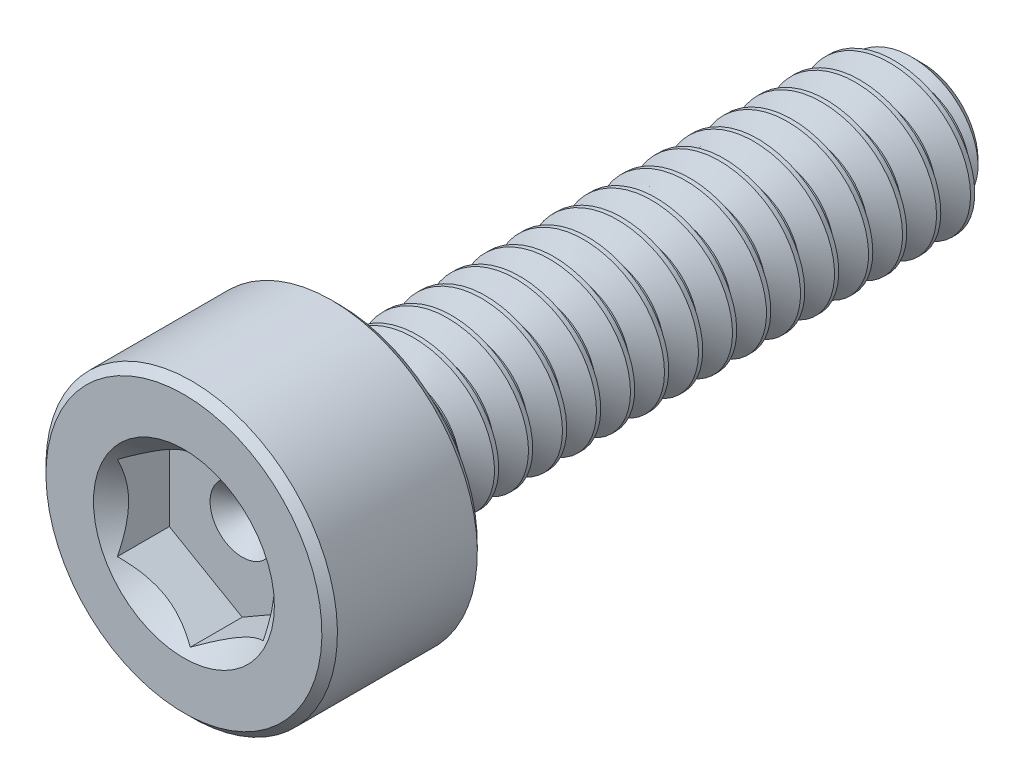
SolidWorks part; units mm, degrees
ref_plane "Front Plane" through (0, 0, 0) normal (0, 0, 1) x (1, 0, 0)
ref_plane "Top Plane" through (0, 0, 0) normal (0, 1, 0) x (1, 0, 0)
ref_plane "Right Plane" through (0, 0, 0) normal (1, 0, 0) x (0, 0, -1)
sketch "Sketch1" plane through (0, 0, 0) normal (1, 0, 0) x (0, 0, -1)
  line L0 (-3.8, 0) -> (3.8, 0) construction
  line L1 (3.8, 0) -> (3.8, 0.5727) construction
  line L2 (3.8, 0.5727) -> (3.5727, 0.8) construction
  line L3 (3.5727, 0.8) -> (3.5375, 0.8) construction
  line L4 (3.5375, 0.8) -> (-2.2, 0.8) construction
  line L5 (-2.2, 0.8) -> (-2.2, 1.5) construction
  line L6 (-2.2, 1.5) -> (-3.8, 1.5) construction
  line L7 (-3.8, 1.5) -> (-3.8, 0) construction
  line L8 (3.8, 0.5727) -> (3.8, 0.8) construction
  line L9 (3.7781, 0.8379) -> (3.9531, 0.5348) construction
  line L10 (3.9531, 0.5348) -> (4.1281, 0.8379) construction
  line L11 (4.1281, 0.8379) -> (3.7781, 0.8379) construction
  line L12 (3.9531, 0.8379) -> (3.9531, 0.8) construction
  line L13 (3.9531, 0.5348) -> (3.9531, 0.5727) construction
  line L14 (3.9312, 0.5727) -> (3.975, 0.5727) construction
  line L15 (3.8, 0.8) -> (4.1063, 0.8) construction
  line L16 (3.7891, 0.8189) -> (4.1172, 0.8189) construction
  line L17 (3.8, 0) -> (3.8, -0.8) construction
  line L18 (-2.28, 1.5) -> (-2.2, 1.42) construction
  line L19 (-3.72, 1.5) -> (-3.8, 1.42) construction
  line L20 (-2.2, 0.8) -> (-2.2, 0) construction
  line L21 (-2.2, 0.4) -> (-0.2, 0.4) construction
  line L22 (-0.2, 0.4) -> (1.8, 0.4) construction
  line L23 (1.8, 0.4) -> (3.8, 0.4) construction
  line L24 (-0.2, 0.4) -> (-0.2, 0.8) construction
  line L25 (-0.2, 0.8) -> (-0.2, 1.5) construction
  line L26 (1.8, 0.4) -> (1.8, 1.5) construction
  point P0 (-3.8, 0.75)
  point P3 (2.925, 0.8)
  point P4 (0, 0)
  point P18 (1.8, 0.8)
  point P22 (3.9531, 0.5727)
  point P24 (3.5375, 0.8)
  point P25 (3.9531, 0.8)
  point P28 (3.9531, 0.8189)
  point P29 (2.925, -0.8)
  point P30 (-0.2, 0.8)
  point P31 (-3, 1.5)
  point P37 (-2.48, 1.5)
  point P38 (-3.68, 1.5)
  point P45 (-0.2, 0.4)
  point P46 (1.8, 0.4)
  dimension "D2" = 0.0437
  dimension "D7" = 0.08
  dimension "D8" = 0.08
  dimension "D9" = 0.08
  dimension "D10" = 0.04
  dimension "D11" = 0.2
  dimension "Drive Size" = 1.5
  dimension "Head Diameter" = 3
  dimension "Head Height" = 1.6
  dimension "Thread Pitch" = 0.35
  dimension "Thread Dia" = 1.6
  dimension "Length" = 6
  dimension "D12" = 0.2625
  dimension "D4" = 0.875
  dimension "D3" = 45
sketch "Sketch2" plane through (0, 0, 0) normal (1, 0, 0) x (0, 0, -1)
  line L0 (-3.8, 0) -> (-3.8, 1.42)
  line L1 (-3.72, 1.5) -> (-2.28, 1.5)
  line L2 (-2.2, 1.42) -> (-2.2, 0.88)
  line L4 (3.5727, 0.8) -> (3.8, 0.5727)
  line L5 (3.8, 0.5727) -> (3.8, 0)
  line L6 (-2.2, 1.5) -> (-3.8, 1.5) construction
  line L7 (3.8, 0) -> (-3.8, 0)
  line L8 (-3.72, 1.5) -> (-3.8, 1.42) construction
  line L10 (-3.72, 1.5) -> (-3.8, 1.42)
  line L14 (-2.28, 1.5) -> (-2.2, 1.42) construction
  line L16 (-2.28, 1.5) -> (-2.2, 1.42)
  line L17 (-2.2, 0.8) -> (-2.2, 1.5) construction
  line L19 (-2.12, 0.8) -> (3.5727, 0.8)
  line L20 (3.5375, 0.8) -> (-2.2, 0.8) construction
  arc A1 (-2.2, 0.88) -> (-2.12, 0.8) centre (-2.12, 0.88) ccw
  dimension "D3" = 0.08
revolve "Revolve1" add sketch "Sketch2" angle 360 about L7
sketch "Sketch3" plane through (0, 0, 3.8) normal (0, 0, 1) x (1, 0, 0)
  line L1 (0.75, -0.433) -> (0.75, 0.433)
  line L2 (0.75, 0.433) -> (0, 0.866)
  line L3 (0, 0.866) -> (-0.75, 0.433)
  line L4 (-0.75, 0.433) -> (-0.75, -0.433)
  line L5 (-0.75, -0.433) -> (0, -0.866)
  line L6 (0, -0.866) -> (0.75, -0.433)
  circle A0 centre (0, 0) radius 0.75 construction
  circle A1 centre (0, 0) radius 1.5 construction
  circle A2 centre (0, 0) radius 1.5 construction
  circle A3 centre (0, 0) radius 0.866 construction
  point P13 (0, 0)
  dimension "D1" = 1.7321
extrude "Cut-Extrude1" cut sketch "Sketch3" against normal offset from surface (0.6 mm away) 1 up to face at (0, 1.42, 2.2)
sketch "Sketch4" plane through (0, 0, 3.8) normal (0, 0, 1) x (1, 0, 0)
  circle A0 centre (0, 0) radius 0.931
  dimension "D1" = 1.862
extrude "Cut-Extrude2" cut sketch "Sketch4" against normal up to vertex (0.8 mm away) draft 45 up to point (0, 1.5, 3)
sketch "Sketch11" plane through (0, 0, 0) normal (1, 0, 0) x (0, 0, -1)
  line L0 (-3.8, 0) -> (3.8, 0) construction
  line L1 (-3.8, 0) -> (3.8, 0) construction
  line L2 (-1.075, 0) -> (-1.075, 0.8) construction
  line L3 (3.5375, 0.8) -> (-2.2, 0.8) construction
  line L4 (2.675, 0) -> (2.675, 0.8) construction
  line L6 (3.8, 0.5727) -> (3.8, 0.8) construction
  point P2 (-1.075, 0)
  point P3 (2.675, 0)
  dimension "D1" = 1.125
  dimension "D2" = 1.125
sketch "Sketch6" plane through (0, 0, -3.8) normal (0, 0, -1) x (-1, 0, 0)
  circle A0 centre (0, 0) radius 0.8
curve "Helix/Spiral1" pitch 0.35 height 6.35 turns 18.1429
sketch "Sketch10" plane through (0, 0, 0) normal (1, 0, 0) x (0, 0, -1)
  line L0 (-2.12, -1.5) -> (-2.12, 1.5)
  line L5 (-3.8, 0) -> (3.8, 0) construction
  line L6 (-2.12, 0.8) -> (-2.12, -0.8) construction
  point P3 (-2.12, 0)
split "Split1" trim tools "Sketch10" bodies to split 106 resulting bodies 114 115
sketch "Sketch7" plane through (0, 0, 0) normal (1, 0, 0) x (0, 0, -1)
  line L0 (3.7891, 0.8189) -> (4.1172, 0.8189)
  line L1 (4.1172, 0.8189) -> (3.975, 0.5727)
  line L2 (3.975, 0.5727) -> (3.9312, 0.5727)
  line L3 (3.9312, 0.5727) -> (3.7891, 0.8189)
sweep "Cut-Sweep1" cut profiles "Sketch7" path "Helix/Spiral1" align with end faces yes
sketch "Sketch8" plane through (0, 0, 0) normal (1, 0, 0) x (0, 0, -1)
  line L0 (-2.2, 0) -> (-2.2, 0.8)
  line L1 (-2.12, -0.8) -> (-2.12, 0.8) construction
  line L2 (-2.2, 0.8) -> (-2.12, 0.8)
  line L4 (-2.12, 0.8) -> (-1.6581, 0)
  line L5 (-1.6581, 0) -> (-2.2, 0)
  line L6 (3.5375, 0.8) -> (-2.2, 0.8) construction
  line L7 (-3.8, 0) -> (3.8, 0) construction
  dimension "D1" = 60
revolve "Revolve2" add sketch "Sketch8" angle 360 about L5
equation "\"D2@Sketch1\" = \"Thread Pitch@Sketch1\" / 8"
equation "\"D4@Helix/Spiral1\" = \"Thread Pitch@Sketch1\""
equation "\"D7@Sketch1\" = \"Head Height@Sketch1\" * .05"
equation "\"D8@Sketch1\"=\"D7@Sketch1\""
equation "\"D9@Sketch1\"=\"D7@Sketch1\""
equation "\"D10@Sketch1\"=\"D7@Sketch1\"/2"
equation "\"D11@Sketch1\"=\"D10@Sketch1\"*5"
equation "\"D4@Sketch1\"=\"Thread Pitch@Sketch1\"*2.5"
equation "\"D12@Sketch1\"=\"Thread Pitch@Sketch1\"*.75"
equation "\"D3@Helix/Spiral1\"=\"Length@Sketch1\"+\"Thread Pitch@Sketch1\""
equation "\"D3@Sketch2\"=\"Thread Dia@Sketch1\"*0.05"
equation "\"D1@Sketch11\"=\"Length@Sketch1\"*0.1875"
equation "\"D2@Sketch11\"=\"D1@Sketch11\""
equation "\"D1@Sketch4\"=\"D1@Sketch3\"*1.075"
